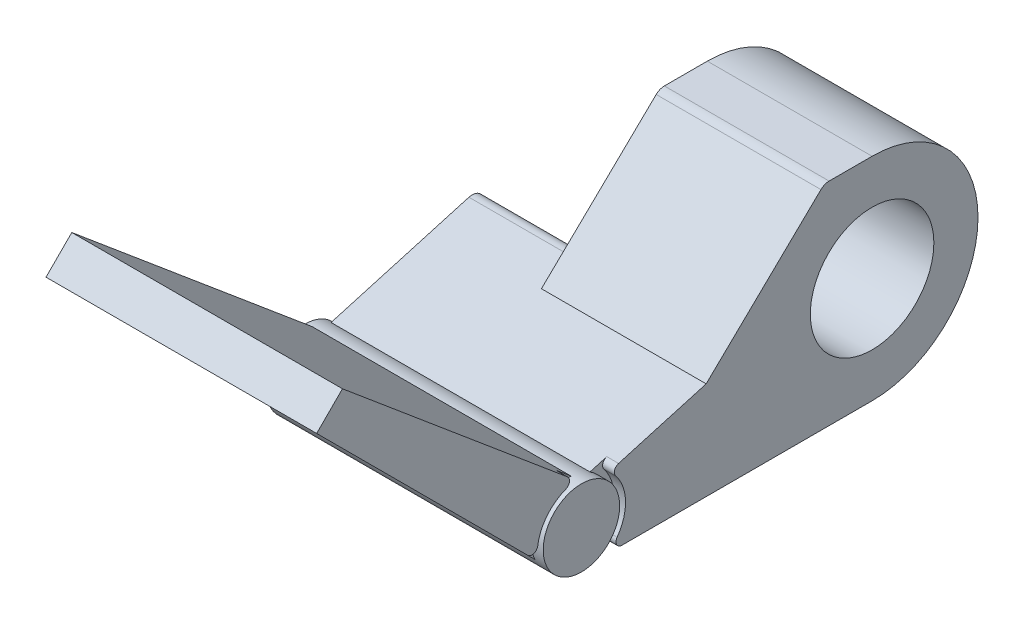
SolidWorks part; units mm, degrees
ref_plane "Front Plane" through (0, 0, 0) normal (0, 0, 1) x (1, 0, 0)
ref_plane "Top Plane" through (0, 0, 0) normal (0, 1, 0) x (1, 0, 0)
ref_plane "Right Plane" through (0, 0, 0) normal (1, 0, 0) x (0, 0, -1)
sketch "Sketch2" plane through (0, 0, 0) normal (1, 0, 0) x (0, 0, -1)
  line L0 (0, 0) -> (-21.2631, 0)
  line L1 (0, 0) -> (0, 18) construction
  line L2 (0, 18) -> (-4.0554, 18)
  line L3 (-4.0554, 18) -> (-14.1, 8.3)
  line L4 (-14.1, 8.3) -> (-21.5434, 6.1656)
  line L5 (-25.8941, 7.3536) -> (-45.008, 23.392)
  line L6 (-45.008, 23.392) -> (-47.2, 21.2)
  line L7 (-47.2, 21.2) -> (-29.2592, 3.2592)
  line L8 (-47.2, 21.2) -> (-27.6616, 1.6616)
  line L9 (-21.2631, 0) -> (-23.45, 0)
  line L10 (-21.5434, 6.1656) -> (-22.9758, 5.7549)
  line L11 (-25.8941, 7.3536) -> (-24.5761, 6.2476)
  arc A0 (0, 0) -> (0, 18) centre (0, 9) ccw
  circle A1 centre (-24.7, 3) radius 3.25
  arc A2 (-21.6674, 0.7941) -> (-21.7932, 5.3691) centre (-24.7, 3) ccw
  circle A3 centre (0, 9) radius 5.25
  arc A4 (-21.7932, 5.3691) -> (-21.6674, 0.7941) centre (-24.7, 3) cw
  arc A5 (-21.5434, 6.1656) -> (-21.7932, 5.3691) centre (-21.4056, 5.685) ccw
  arc A6 (-21.2631, 0) -> (-21.6674, 0.7941) centre (-21.2631, 0.5) cw
  arc A7 (-28.4108, 3.5406) -> (-26.0372, 6.5035) centre (-24.7, 3) cw
  arc A8 (-26.0372, 6.5035) -> (-25.8941, 7.3536) centre (-26.2155, 6.9706) ccw
  arc A9 (-28.4108, 3.5406) -> (-29.2592, 3.2592) centre (-28.9056, 3.6127) cw
  arc A10 (-26.0372, 6.5035) -> (-28.4108, 3.5406) centre (-24.7, 3) ccw
  point P11 (-23.45, 0)
  point P14 (-22.3611, 5.9312)
  point P15 (-24.5761, 6.2476)
  dimension "D1" = 10.5
  dimension "D2" = 18
  dimension "D8" = 6.5
  dimension "D9" = 7.5
  dimension "D11" = 0.5
  dimension "D3" = 0.5
  dimension "D18" = 0.5
  dimension "D19" = 0.5
  dimension "D4" = 152
  dimension "D5" = 16
  dimension "D6" = 24.7
  dimension "D7" = 3
  dimension "D10" = 14.1
  dimension "D12" = 8.3
  dimension "D13" = 3.1
  dimension "D14" = 5
  dimension "D15" = 135
  dimension "D16" = 47.2
  dimension "D17" = 21.2
extrude "Boss-Extrude1" add sketch "Sketch2" against normal blind 14 contours A9 A7 A8 L5 L6 L7 | A1 | L0 L1 A3 L2 L3 L4 A5 A2 A6 | L1 A0 A3 | A7 A9 L8 A1 L11 A8 | L9 A6 A2 A5 L10 A1 region at (0, 6.3808, 9.7602) region at (0, 1.875, -0.2012) region at (0, 0.0665, 22.3565) region at (0, 3, 24.7) region at (0, 2.5125, 28.4083) region at (0, 12.9766, 35.9509)
extrude "Cut-Extrude1" cut sketch "Sketch2<5>" against normal blind 1 contours A7 A9 L8 A1 L11 A8 region at (0, 2.5125, 28.4083)
sketch "Sketch2<5>" plane through (0, 0, 0) normal (1, 0, 0) x (0, 0, -1) same geometry as "Sketch2"
extrude "Cut-Extrude2" cut sketch "Sketch2<6>" against normal blind 1 contours L9 A6 A2 A5 L10 A1 region at (0, 0.0665, 22.3565)
sketch "Sketch2<6>" plane through (0, 0, 0) normal (1, 0, 0) x (0, 0, -1) same geometry as "Sketch2"
sketch "Sketch3" plane through (-14, 0, 0) normal (-1, 0, 0) x (0, 0, 1)
  line L0 (0, 0) -> (0, 14.25) construction
  line L1 (45.008, 23.392) -> (24.5761, 6.2476)
  line L2 (45.008, 23.392) -> (47.2, 21.2)
  line L3 (47.2, 21.2) -> (27.6616, 1.6616)
  line L4 (22.9758, 5.7549) -> (11.2596, 9.1145)
  line L5 (23.45, 0) -> (7.5739, 0)
  line L7 (14.1, 8.3) -> (22.9758, 5.7549) construction
  line L8 (0, 0) -> (23.45, 0) construction
  circle A0 centre (0, 9) radius 5.25 construction
  circle A1 centre (0, 9) radius 5.25
  arc A2 (6.8864, 1.7262) -> (9.9869, 8.2301) centre (0, 9) ccw
  circle A3 centre (24.7, 3) radius 3.25
  arc A4 (9.9869, 8.2301) -> (6.8864, 1.7262) centre (0, 9) cw
  arc A5 (9.9869, 8.2301) -> (11.2596, 9.1145) centre (10.984, 8.1532) cw
  arc A6 (7.5739, 0) -> (6.8864, 1.7262) centre (7.5739, 1) cw
  point P26 (8.2972, 3.3887)
  point P32 (10.0053, 9.4741)
  line M5 (47.2, 21.2) -> (45.008, 23.392)
  line M6 (45.008, 23.392) -> (24.5761, 6.2476)
  arc M7 (24.5761, 6.2476) -> (22.9758, 5.7549) centre (24.7, 3) ccw
  line M8 (22.9758, 5.7549) -> (14.1, 8.3)
  line M12 (0, 0) -> (23.45, 0)
  arc M13 (23.45, 0) -> (27.6616, 1.6616) centre (24.7, 3) ccw
  line M14 (27.6616, 1.6616) -> (47.2, 21.2)
  dimension "D1" = 10.5
  dimension "D2" = 20.0331
  dimension "D3" = 6.5
  dimension "D4" = 1
  dimension "D5" = 1
extrude "Boss-Extrude2" add sketch "Sketch3" along normal blind 9 contours A6 A3 L4 A5 A2 M12 M8 | A3 M7 M13 | A3 M14 M5 M6 region at (-14, 12.7068, 35.6636) region at (-14, 3, 24.7) region at (-14, 3.7232, 14.7638)
extrude "Boss-Extrude3" add sketch "Sketch3<3>" along normal blind 9.5 contours A3 M7 M13 region at (-14, 3, 24.7)
sketch "Sketch3<3>" plane through (-14, 0, 0) normal (-1, 0, 0) x (0, 0, 1) same geometry as "Sketch3"
fillet "Fillet1" radius 1 1 edges at (-7, 18, 4.0554)
